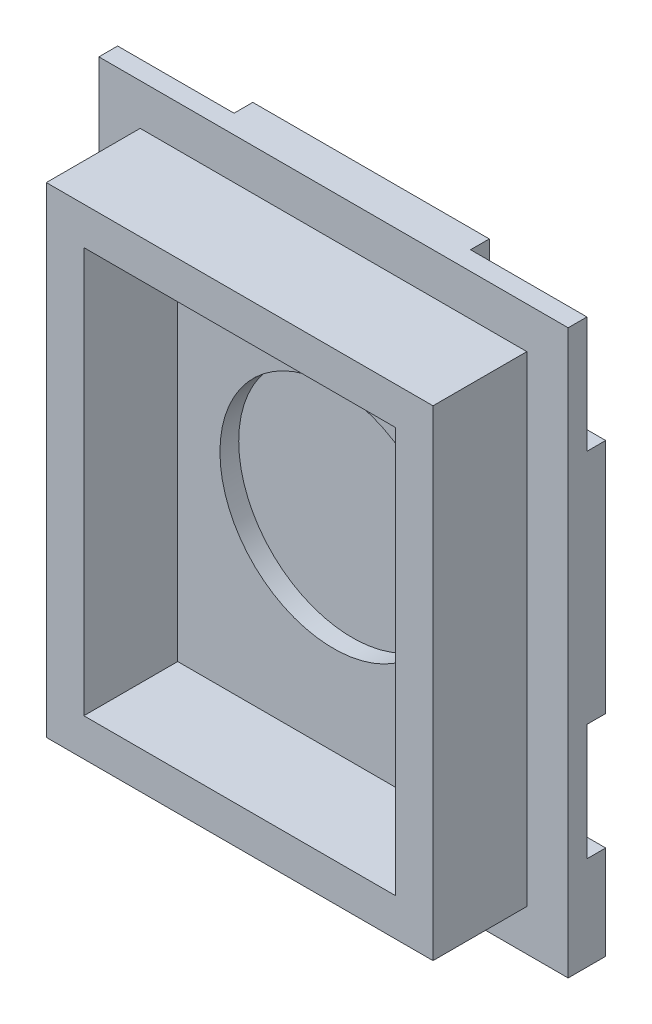
SolidWorks part; units mm, degrees
ref_plane "正面" through (0, 0, 0) normal (0, 0, 1) x (1, 0, 0)
ref_plane "平面" through (0, 0, 0) normal (0, 1, 0) x (1, 0, 0)
ref_plane "右側面" through (0, 0, 0) normal (1, 0, 0) x (0, 0, -1)
sketch "ｽｹｯﾁ1" plane through (0, 0, 0) normal (0, 0, 1) x (1, 0, 0)
  line L1 (-36.7373, 39.7071) -> (-11.7373, 39.7071)
  line L2 (-36.7373, 39.7071) -> (-36.7373, 9.7071)
  line L3 (-36.7373, 9.7071) -> (-11.7373, 9.7071)
  line L4 (-11.7373, 39.7071) -> (-11.7373, 9.7071)
  dimension "D3" = 25
  dimension "D4" = 30
extrude "ﾎﾞｽ - 押し出し1" add sketch "ｽｹｯﾁ1" along normal blind 2
sketch "ｽｹｯﾁ2" plane through (0, 0, 2) normal (0, 0, 1) x (1, 0, 0)
  line L0 (-11.7373, 39.7071) -> (-36.7373, 39.7071) construction
  line L1 (-13.9373, 37.5071) -> (-34.5373, 37.5071)
  line L2 (-13.9373, 37.5071) -> (-13.9373, 11.9071)
  line L3 (-13.9373, 11.9071) -> (-34.5373, 11.9071)
  line L4 (-34.5373, 37.5071) -> (-34.5373, 11.9071)
  line L5 (-36.7373, 9.7071) -> (-11.7373, 9.7071) construction
  line L6 (-36.7373, 39.7071) -> (-36.7373, 9.7071) construction
  line L7 (-11.7373, 9.7071) -> (-11.7373, 39.7071) construction
  dimension "D2" = 2.2
  dimension "D3" = 2.2
  dimension "D4" = 2.2
  dimension "D5" = 2.2
extrude "ﾎﾞｽ - 押し出し2" add sketch "ｽｹｯﾁ2" along normal blind 5
sketch "ｽｹｯﾁ3" plane through (0, 0, 7) normal (0, 0, 1) x (1, 0, 0)
  line L0 (-13.9373, 37.5071) -> (-34.5373, 37.5071) construction
  line L1 (-32.5373, 13.9071) -> (-15.9373, 13.9071)
  line L2 (-32.5373, 13.9071) -> (-32.5373, 35.5071)
  line L3 (-32.5373, 35.5071) -> (-15.9373, 35.5071)
  line L4 (-15.9373, 13.9071) -> (-15.9373, 35.5071)
  line L5 (-34.5373, 11.9071) -> (-13.9373, 11.9071) construction
  line L6 (-13.9373, 11.9071) -> (-13.9373, 37.5071) construction
  line L7 (-34.5373, 37.5071) -> (-34.5373, 11.9071) construction
  dimension "D1" = 21.6
  dimension "D2" = 16.6
  dimension "D3" = 2
  dimension "D4" = 2
  dimension "D5" = 2
  dimension "D6" = 2
extrude "ｶｯﾄ - 押し出し1" cut sketch "ｽｹｯﾁ3" against normal blind 5
sketch "ｽｹｯﾁ4" plane through (0, 0, 0) normal (0, 0, -1) x (-1, 0, 0)
  line L0 (11.7373, 39.7071) -> (36.7373, 39.7071) construction
  line L1 (11.7373, 39.7071) -> (17.9373, 39.7071)
  line L2 (11.7373, 39.7071) -> (11.7373, 33.5071)
  line L3 (11.7373, 33.5071) -> (17.9373, 33.5071)
  line L4 (17.9373, 39.7071) -> (17.9373, 33.5071)
  line L5 (36.7373, 39.7071) -> (30.5373, 39.7071)
  line L6 (36.7373, 39.7071) -> (36.7373, 33.5071)
  line L7 (36.7373, 33.5071) -> (30.5373, 33.5071)
  line L8 (30.5373, 39.7071) -> (30.5373, 33.5071)
  line L9 (37.7373, 14.7071) -> (31.5373, 14.7071)
  line L10 (37.7373, 14.7071) -> (37.7373, 20.9071)
  line L11 (37.7373, 20.9071) -> (31.5373, 20.9071)
  line L12 (31.5373, 14.7071) -> (31.5373, 20.9071)
  line L13 (11.7373, 14.7071) -> (17.9373, 14.7071)
  line L14 (11.7373, 14.7071) -> (11.7373, 20.9071)
  line L15 (11.7373, 20.9071) -> (17.9373, 20.9071)
  line L16 (17.9373, 14.7071) -> (17.9373, 20.9071)
  dimension "D1" = 6.2
  dimension "D2" = 6.2
  dimension "D3" = 6.2
  dimension "D4" = 6.2
  dimension "D5" = 6.2
  dimension "D6" = 6.2
  dimension "D7" = 6.2
  dimension "D8" = 25
  dimension "D9" = 25
extrude "ｶｯﾄ - 押し出し2" cut sketch "ｽｹｯﾁ4" against normal blind 1
sketch "ｽｹｯﾁ5" plane through (0, 0, 2) normal (0, 0, 1) x (1, 0, 0)
  line L0 (-36.7373, 39.7071) -> (-36.7373, 9.7071) construction
  line L1 (-11.7373, 39.7071) -> (-36.7373, 39.7071) construction
  circle A0 centre (-24.2373, 24.7071) radius 6.05
  dimension "D1" = 12.1
  dimension "D2" = 12.5
  dimension "D3" = 15
extrude "ｶｯﾄ - 押し出し3" cut sketch "ｽｹｯﾁ5" against normal blind 1
